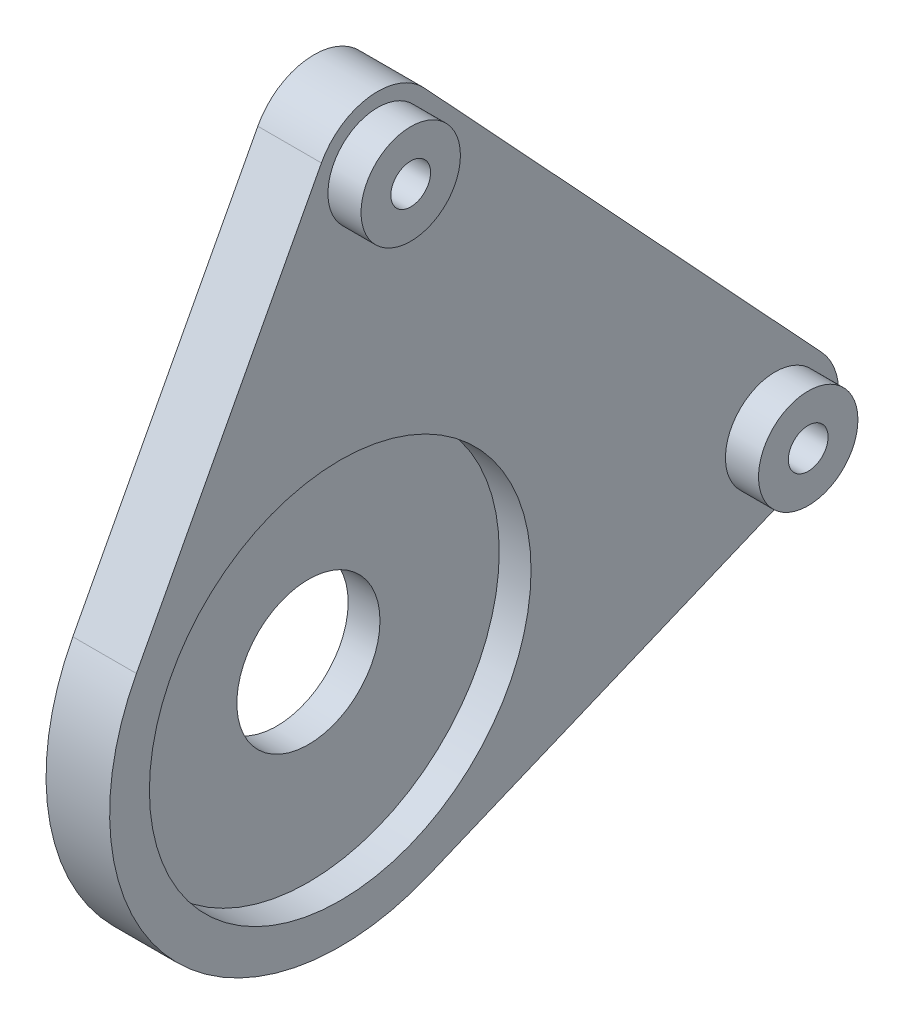
SolidWorks part; units mm, degrees
ref_plane "Front Plane" through (0, 0, 0) normal (0, 0, 1) x (1, 0, 0)
ref_plane "Top Plane" through (0, 0, 0) normal (0, 1, 0) x (1, 0, 0)
ref_plane "Right Plane" through (0, 0, 0) normal (1, 0, 0) x (0, 0, -1)
sketch "Sketch1" plane through (0, 0, 0) normal (1, 0, 0) x (0, 0, -1)
  line L0 (-1.1823, 28.7681) -> (-12.8163, 6.7817)
  line L1 (5.2833, 29.6203) -> (30.28, 2.723)
  line L2 (28.8856, -3.6935) -> (5.5667, -13.3889)
  line L3 (2.3532, 26.8973) -> (0, 0) construction
  line L4 (0, 0) -> (0, 26.8973) construction
  line L5 (0, 26.8973) -> (2.3532, 26.8973) construction
  circle A0 centre (0, 0) radius 4.5
  circle A1 centre (2.3532, 26.8973) radius 1.25
  circle A2 centre (27.35, 0) radius 1.25
  circle A3 centre (0, 0) radius 12
  circle A4 centre (27.35, 0) radius 4
  circle A5 centre (2.3532, 26.8973) radius 4
  circle A6 centre (0, 0) radius 14.5
  circle A7 centre (2.3532, 26.8973) radius 3.125
  circle A8 centre (27.35, 0) radius 3.125
  dimension "D1" = 2.5
  dimension "D2" = 9
  dimension "D3" = 24
  dimension "D6" = 8
  dimension "D7" = 8
  dimension "D8" = 29
  dimension "D9" = 6.25
  dimension "D4" = 27
  dimension "D5" = 27.35
  dimension "D10" = 5
extrude "Boss-Extrude1" add sketch "Sketch1" along normal blind 4 contours A6 A3 | A6 L2 A4 L1 A5 L0 | A5 A1 | A4 A2 | A7 A1 | A8 A2 region at (0, 10.3327, -11.5599) region at (0, 30.7508, -1.8453) region at (0, 13.6748, -3.395) region at (0, 1.4215, -30.9676) region at (0, 26.8973, 0.6834) region at (0, 0, -24.3134)
extrude "Boss-Extrude2" add sketch "Sketch1<3>" along normal blind 6.08 contours A7 A1 | A8 A2 region at (0, 26.8973, 0.6834) region at (0, 0, -24.3134)
sketch "Sketch1<3>" plane through (0, 0, 0) normal (1, 0, 0) x (0, 0, -1) same geometry as "Sketch1"
extrude "Boss-Extrude3" add sketch "Sketch1<4>" along normal blind 2 contours A3 A0 region at (0, 0, 11.6606)
sketch "Sketch1<4>" plane through (0, 0, 0) normal (1, 0, 0) x (0, 0, -1) same geometry as "Sketch1"
move or copy body "Body-Move/Copy1" [suppressed] bodies to move or copy 103
equation "\"D5@Sketch1\"=21.60mm+2.5/2+9/2"
